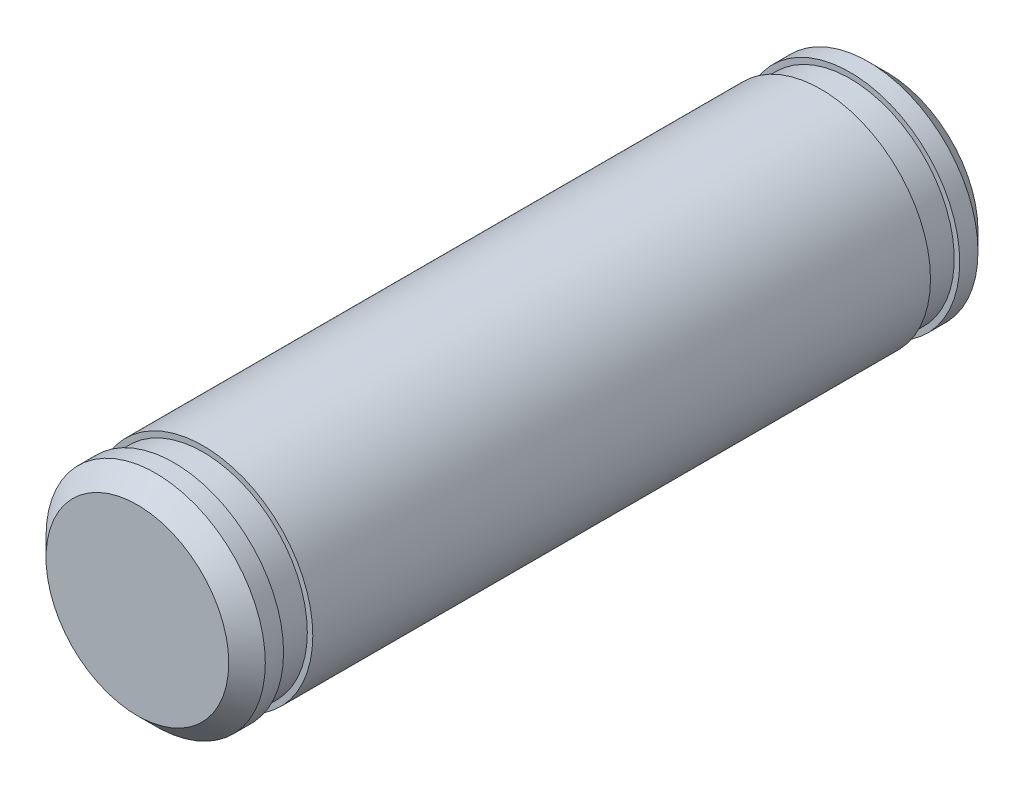
SolidWorks part; units mm, degrees
material "Stop 1060"
ref_plane "Płaszczyzna przednia" through (0, 0, 0) normal (0, 0, 1) x (1, 0, 0)
ref_plane "Płaszczyzna górna" through (0, 0, 0) normal (0, 1, 0) x (1, 0, 0)
ref_plane "Płaszczyzna prawa" through (0, 0, 0) normal (1, 0, 0) x (0, 0, -1)
sketch "Szkic1" plane through (0, 0, 0) normal (0, 0, 1) x (1, 0, 0)
  circle A0 centre (0, 0) radius 3
  dimension "D1" = 6
extrude "Dodanie-wyciągnięcie1" add sketch "Szkic1" along normal blind 20.5
chamfer "Sfazowanie1" distance 0.5 angle 45 2 edges at (3, 0, 0) (3, 0, 20.5)
sketch "Szkic2" plane through (0, 0, 20.5) normal (0, 0, 1) x (1, 0, 0)
  circle A0 centre (0, 0) radius 3
  circle A1 centre (0, 0) radius 2.85
  dimension "D1" = 6
  dimension "D2" = 5.7
extrude "Wytnij-wyciągnięcie1" cut sketch "Szkic2" against normal blind 0.8 from offset 1 offset against normal yes
sketch "Szkic3" plane through (0, 0, 0) normal (0, 0, -1) x (-1, 0, 0)
  circle A0 centre (0, 0) radius 3
  circle A1 centre (0, 0) radius 2.85
  dimension "D1" = 6
  dimension "5,6" = 5.7
extrude "Wytnij-wyciągnięcie2" cut sketch "Szkic3" against normal blind 0.8 from offset 1 offset against normal yes
